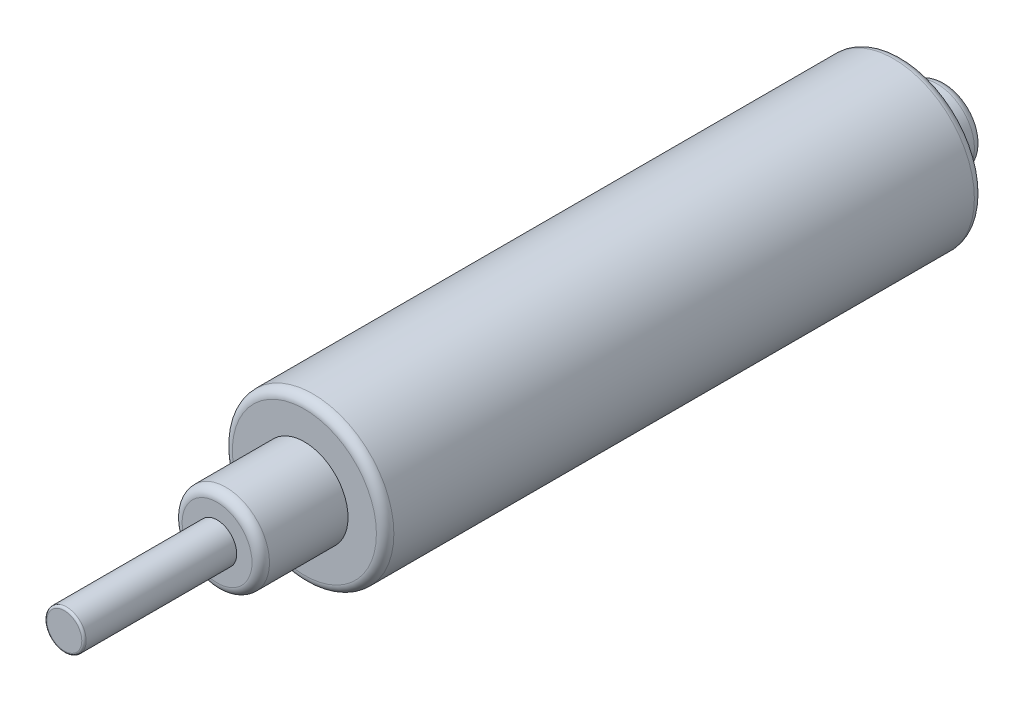
SolidWorks part; units mm, degrees
ref_plane "Front Plane" through (0, 0, 0) normal (0, 0, 1) x (1, 0, 0)
ref_plane "Top Plane" through (0, 0, 0) normal (0, 1, 0) x (1, 0, 0)
ref_plane "Right Plane" through (0, 0, 0) normal (1, 0, 0) x (0, 0, -1)
sketch "Sketch1" plane through (0, 0, 0) normal (0, 0, 1) x (1, 0, 0)
  circle A0 centre (0, 0) radius 18.5
  point P0 (0, 0)
  dimension "D1" = 37
extrude "Boss-Extrude1" add sketch "Sketch1" along normal blind 137
sketch "Sketch2" plane through (0, 0, 137) normal (0, 0, 1) x (1, 0, 0)
  circle A0 centre (0, 0) radius 10
  dimension "D1" = 20
extrude "Boss-Extrude2" add sketch "Sketch2" along normal blind 20
sketch "Sketch3" plane through (0, 0, 0) normal (0, 0, -1) x (-1, 0, 0)
  circle A0 centre (0, 0) radius 8.5
  dimension "D1" = 17
extrude "Boss-Extrude3" add sketch "Sketch3" along normal blind 10
fillet "Fillet1" radius 2 4 edges at (10, 0, 157) (18.5, 0, 137) (18.5, 0, 0) (-8.5, 0, -10)
sketch "Sketch4" plane through (0, 0, -10) normal (0, 0, -1) x (-1, 0, 0)
  circle A0 centre (0, 0) radius 4.5
  dimension "D1" = 9
extrude "Cut-Extrude1" cut sketch "Sketch4" against normal up to surface (10 mm away) up to face at (16.5, 0, 0)
sketch "Sketch5" plane through (0, 0, 157) normal (0, 0, 1) x (1, 0, 0)
  circle A0 centre (0, 0) radius 4
  dimension "D1" = 8
extrude "Cut-Extrude2" cut sketch "Sketch5" against normal up to surface (20 mm away) up to face at (16.5, 0, 137)
sketch "Sketch6" plane through (0, 0, 137) normal (0, 0, 1) x (1, 0, 0)
  circle A0 centre (0, 0) radius 1
  dimension "D1" = 2
extrude "Boss-Extrude4" add sketch "Sketch6" along normal up to surface (20 mm away) up to face at (4, 0, 157)
fillet "Fillet2" radius 0.5 2 edges at (1, 0, 157) (4, 0, 157)
sketch "Sketch8" plane through (0, 0, 157) normal (0, 0, 1) x (1, 0, 0)
  circle A0 centre (0, 0) radius 4.5
extrude "Boss-Extrude5" add sketch "Sketch8" along normal blind 35 separate body
fillet "Fillet3" radius 0.5 1 edges at (4.5, 0, 192)
